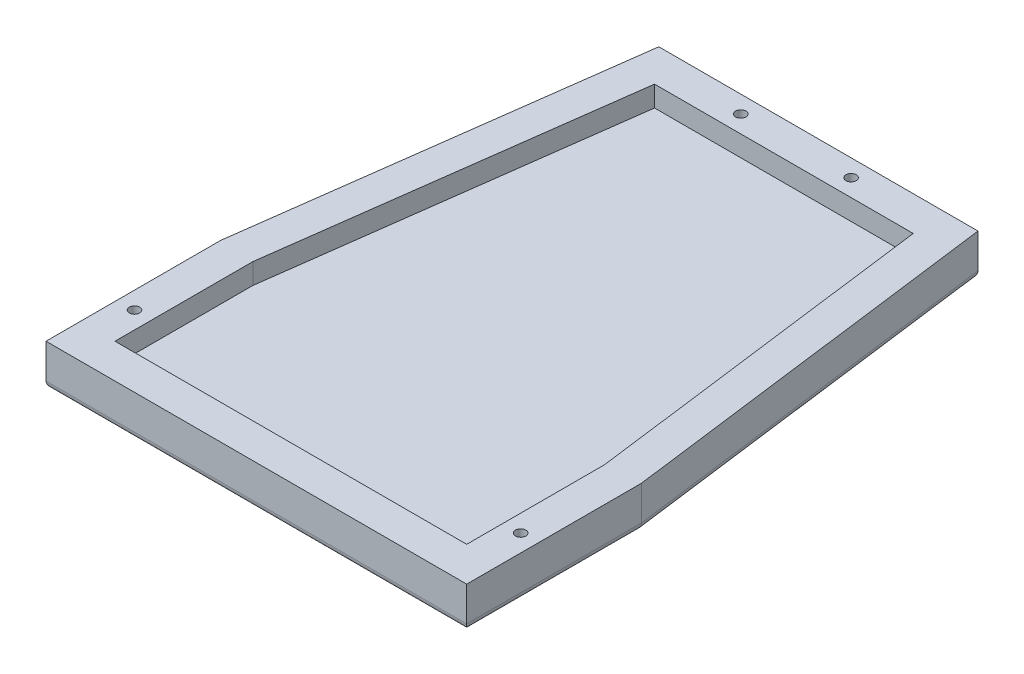
SolidWorks part; units mm, degrees
ref_plane "Płaszczyzna przednia" through (0, 0, 0) normal (0, 0, 1) x (1, 0, 0)
ref_plane "Płaszczyzna górna" through (0, 0, 0) normal (0, 1, 0) x (1, 0, 0)
ref_plane "Płaszczyzna prawa" through (0, 0, 0) normal (1, 0, 0) x (0, 0, -1)
sketch "Szkic1" plane through (0, 0, 0) normal (0, 1, 0) x (1, 0, 0)
  line L0 (-46.2252, 44.9878) -> (-0.2252, 44.9878)
  line L1 (-0.2252, 44.9878) -> (7.2748, -12.8855)
  line L2 (7.2748, -12.8855) -> (7.2748, -36.4122)
  line L3 (7.2748, -36.4122) -> (-53.7252, -36.4122)
  line L4 (-53.7252, -36.4122) -> (-53.7252, -11.4122)
  line L5 (-53.7252, -11.4122) -> (-46.2252, 44.9878)
  dimension "D1" = 46
  dimension "D2" = 61
  dimension "D3" = 7.5
  dimension "D4" = 56.4
  dimension "D5" = 25
  dimension "D6" = 7.5
extrude "Dodanie-wyciągnięcie1" add sketch "Szkic1" along normal blind 3
sketch "Szkic3" plane through (0, 0, 0) normal (0, 1, 0) x (1, 0, 0)
  line L0 (-48.7252, -31.4122) -> (2.2748, -31.4122)
  line L1 (-53.7252, -11.4122) -> (-53.7252, -36.4122) construction
  line L2 (7.2748, -36.4122) -> (7.2748, -12.8855) construction
  line L3 (-48.7252, -31.4122) -> (-48.7252, -11.4122)
  line L4 (-53.7252, -36.4122) -> (7.2748, -36.4122) construction
  line L5 (-41.8901, 39.9878) -> (-4.3863, 39.9878)
  line L6 (-0.2252, 44.9878) -> (-46.2252, 44.9878) construction
  line L7 (-4.3863, 39.9878) -> (2.2748, -11.4122)
  line L8 (-48.7252, -11.4122) -> (-41.8901, 39.9878)
  line L9 (2.2748, -31.4122) -> (2.2748, -11.4122)
  line L10 (-46.2252, 44.9878) -> (-53.7252, -11.4122) construction
  line L11 (7.2748, -12.8855) -> (-0.2252, 44.9878) construction
  dimension "D1" = 51
  dimension "D2" = 5
  dimension "D3" = 5
  dimension "D4" = 5
  dimension "D5" = 20
  dimension "D6" = 5
  dimension "D7" = 0
  dimension "D8" = 0
  dimension "D9" = 20
extrude "Wyciągnięcie-cienka ścianka1" add sketch "Szkic3" along normal blind 6 from offset 0 thin contours L7 L9 L0 L3 L8 L5 thin type one direction wall 5
sketch "Szkic5" plane through (0, 6, 0) normal (0, 1, 0) x (1, 0, 0)
  line L0 (-46.2692, 44.9878) -> (0.0075, 44.9878) construction
  line L1 (7.2748, -36.4122) -> (7.2748, -11.0896) construction
  line L2 (-53.7252, -36.4122) -> (-53.7252, -11.0812) construction
  circle A0 centre (-31.8901, 42.4878) radius 0.75
  circle A1 centre (-15.8901, 42.4878) radius 0.75
  circle A2 centre (-51.2252, -26.0812) radius 0.75
  circle A3 centre (4.7748, -26.0896) radius 0.75
  dimension "D3" = 1.5
  dimension "D4" = 1.5
  dimension "D8" = 1.5
  dimension "D9" = 1.5
  dimension "D1" = 2.5
  dimension "D2" = 2.5
  dimension "D5" = 16
  dimension "D6" = 10
  dimension "D7" = 11.5038
  dimension "D10" = 2.5
  dimension "D11" = 2.5
  dimension "D12" = 15
  dimension "D13" = 15
extrude "Wytnij-wyciągnięcie1" cut sketch "Szkic5" against normal blind 39 and the other way blind 51
fillet "Zaokrąglenie1" radius 1 10 edges at (-23.1308, 0, -44.9878) (-49.9972, 0, -16.9533) (-53.7252, 0, 23.7467) (-23.2252, 0, 36.4122) (7.2748, 0, 23.7509) (3.6412, 0, -16.9491) (-31.8901, 0, -43.2378) (-15.8901, 0, -43.2378) (4.7748, 0, 25.3396) (-51.2252, 0, 25.3312)
